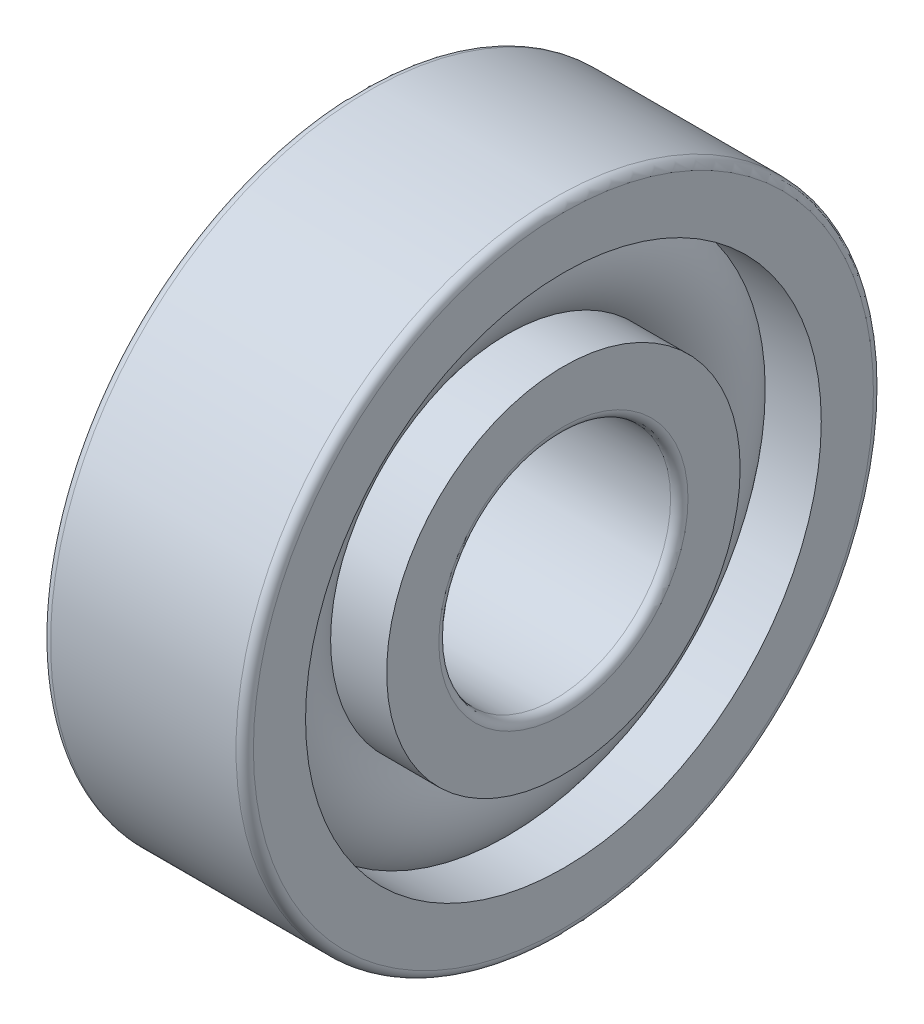
SolidWorks part; units mm, degrees
ref_plane "Plane1" through (0, 0, 0) normal (0, 0, 1) x (1, 0, 0)
ref_plane "Plane2" through (0, 0, 0) normal (0, 1, 0) x (1, 0, 0)
ref_plane "Plane3" through (0, 0, 0) normal (1, 0, 0) x (0, 0, -1)
sketch "Clipboard" plane through (0, 0, 0) normal (0, 0, 1) x (1, 0, 0)
  line L0 (-10, 0) -> (10, 0) construction
  line L1 (0, 0) -> (22.3471, -0.7804)
  line L2 (0, 0) -> (7.4954, 0.2617)
  line L3 (0, 0) -> (22.3471, -0.7804)
  line L4 (0, 0) -> (-22.3573, -0.3902)
sketch "CagSpiSke" plane through (0, 0, 0) normal (0, 0, 1) x (1, 0, 0)
  line L0 (0.21, 7.15) -> (0.21, 7.85)
  line L1 (0.21, 7.85) -> (-0.21, 7.85)
  line L2 (-0.21, 7.85) -> (-0.21, 7.15)
  line L3 (-0.21, 7.15) -> (0.21, 7.15)
  line L4 (-20.6375, 0) -> (20.6375, 0) construction
  line L5 (0, 0) -> (0, 23.7692) construction
revolve "CageSpine" add sketch "CagSpiSke" angle 0.001 about L4 reverse direction yes
ref_axis "Axis1" through (-50, 0, 0) along (1, 0, 0)
sketch "CagBalSke" plane through (0, 0, 0) normal (0, 0, 1) x (1, 0, 0)
  line L0 (-2.31, 7.5) -> (2.31, 7.5)
  line L1 (-1.905, 7.5) -> (1.905, 7.5) construction
  line L2 (-10, 0) -> (10, 0) construction
  line L3 (0, 0) -> (0, 24) construction
  arc A0 (2.31, 7.5) -> (-2.31, 7.5) centre (0, 7.5) cw
revolve "CageBall" [suppressed] add sketch "CagBalSke" angle 360 about L1 reverse direction yes
pattern_circular "CageBalls" [suppressed] count 2 every 180 about axis through (-50, 0, 0) along (1, 0, 0)
sketch "CagTrmODSke" plane through (0, 0, 0) normal (0, 0, 1) x (1, 0, 0)
  line L0 (2.311, 7.85) -> (2.311, 9.811)
  line L1 (2.311, 9.811) -> (-2.311, 9.811)
  line L2 (-2.311, 9.811) -> (-2.311, 7.85)
  line L3 (-2.311, 7.85) -> (2.311, 7.85)
  line L4 (-20.6375, 0) -> (20.6375, 0) construction
  line L5 (0, 0) -> (0, 25) construction
revolve "CageTrimOD" [suppressed] cut sketch "CagTrmODSke" angle 360 about L4 reverse direction yes
sketch "CagTrmIDSke" plane through (0, 0, 0) normal (0, 0, 1) x (1, 0, 0)
  line L0 (2.311, 5.191) -> (2.311, 7.15)
  line L1 (2.311, 7.15) -> (-2.311, 7.15)
  line L2 (-2.311, 7.15) -> (-2.311, 5.191)
  line L3 (-2.311, 5.191) -> (2.311, 5.191)
  line L4 (-20.6375, 0) -> (20.6375, 0) construction
  line L5 (0, 0) -> (0, 25) construction
revolve "CageTrimID" [suppressed] cut sketch "CagTrmIDSke" angle 360 about L4 reverse direction yes
sketch "BalSimSke" plane through (0, 0, 0) normal (0, 0, 1) x (1, 0, 0)
  line L0 (-10, 0) -> (10, 0) construction
  line L1 (-10, 7.5) -> (10, 7.5) construction
  line L2 (0, 0) -> (0, 23) construction
  circle A0 centre (0, 7.5) radius 2.1
revolve "BallsSimplified" add sketch "BalSimSke" angle 360 about L0
sketch "BalDetSke" plane through (0, 0, 0) normal (0, 0, 1) x (1, 0, 0)
  line L0 (-2.1, 7.5) -> (2.1, 7.5)
  line L1 (-1.905, 7.5) -> (1.905, 7.5) construction
  line L2 (0, 0) -> (0, 25) construction
  arc A0 (2.1, 7.5) -> (-2.1, 7.5) centre (0, 7.5) cw
revolve "BallDetailed" [suppressed] add sketch "BalDetSke" angle 360 about L1 reverse direction yes
sketch "InnRacSke" plane through (0, 0, 0) normal (0, 0, 1) x (1, 0, 0)
  line L0 (-1.5315, 6.1) -> (-3.5, 6.1)
  line L1 (-3.5, 6.1) -> (-3.5, 4.3)
  line L2 (-3.2, 4) -> (3.2, 4)
  line L3 (3.5, 4.3) -> (3.5, 6.1)
  line L4 (3.5, 6.1) -> (1.5315, 6.1)
  line L5 (-20.6375, 0) -> (20.6375, 0) construction
  line L6 (0, 0) -> (0, 30) construction
  arc A0 (-3.5, 4.3) -> (-3.2, 4) centre (-3.2, 4.3) ccw
  arc A1 (3.2, 4) -> (3.5, 4.3) centre (3.2, 4.3) ccw
  arc A2 (1.5315, 6.1) -> (-1.5315, 6.1) centre (0, 7.5) cw
revolve "InnerRace" add sketch "InnRacSke" angle 360 about L5 reverse direction yes
sketch "OutRacSke" plane through (0, 0, 0) normal (0, 0, 1) x (1, 0, 0)
  line L0 (-1.5315, 8.9) -> (-3.5, 8.9)
  line L1 (-3.5, 8.9) -> (-3.5, 10.7)
  line L2 (-3.2, 11) -> (3.2, 11)
  line L3 (3.5, 10.7) -> (3.5, 8.9)
  line L4 (3.5, 8.9) -> (1.5315, 8.9)
  line L5 (-20.6375, 0) -> (20.6375, 0) construction
  line L6 (0, 0) -> (0, 30) construction
  arc A0 (-3.5, 10.7) -> (-3.2, 11) centre (-3.2, 10.7) cw
  arc A1 (3.2, 11) -> (3.5, 10.7) centre (3.2, 10.7) cw
  arc A2 (1.5315, 8.9) -> (-1.5315, 8.9) centre (0, 7.5) ccw
revolve "OuterRace" add sketch "OutRacSke" angle 360 about L5 reverse direction yes
pattern_circular "BallsDetailed" [suppressed] count 2 every 180 about axis through (-50, 0, 0) along (1, 0, 0)
equation "\"BallCLRad@Clipboard\" = ( \"OD@OutRacSke\" + \"ID@InnRacSke\" ) / 4"
equation "\"BallCLRad@BalSimSke\" = \"BallCLRad@Clipboard\""
equation "\"BallCLRad@BalDetSke\" = \"BallCLRad@Clipboard\""
equation "\"BallCLRad@InnRacSke\" = \"BallCLRad@Clipboard\""
equation "\"BallCLRad@OutRacSke\" = \"BallCLRad@Clipboard\""
equation "\"Ball_diameter@InnRacSke\" = \"Ball_diameter@BalDetSke\" - 0.05"
equation "\"Ball_diameter@OutRacSke\" = \"Ball_diameter@BalDetSke\" - 0.05"
equation "\"Ball_diameter@BalSimSke\" = \"Ball_diameter@BalDetSke\""
equation "\"Width@OutRacSke\" = \"Width@InnRacSke\""
equation "\"Fillet_radius@OutRacSke\" = \"Fillet_radius@InnRacSke\""
equation "\"Max_count@Clipboard\" = int( 3.14159265 / atn(( \"Ball_diameter@BalDetSke\" / 2) / sqr( \"BallCLRad@Clipboard\"  *  \"BallCLRad@Clipboard\" - ( \"Ball_diameter@BalDetSke\" / 2) *  ( \"Ball_diameter@BalDetSke\" / 2))))"
equation "\"Max_count@Clipboard\" = ((sgn( \"Max_count@Clipboard\" - \"Count@Clipboard\" )-1)*( \"Max_count@Clipboard\" - \"Count@Clipboard\" ))/-2+ \"Count@Clipboard\""
equation "\"Count@BallsDetailed\" = int( \"Show_count@Clipboard\" ) "
equation "\"Count@BallsDetailed\" = ((sgn( \"Count@BallsDetailed\" - \"Max_count@Clipboard\" )-1)*( \"Count@BallsDetailed\" - \"Max_count@Clipboard\" ))/-2+ \"Max_count@Clipboard\""
equation "\"Count@BallsDetailed\" = ((sgn( \"Count@BallsDetailed\" - \"Min_count@Clipboard\" )+1)*( \"Count@BallsDetailed\" - \"Min_count@Clipboard\"))/2 +\"Min_count@Clipboard\""
equation "\"Angle@BallsDetailed\" = 360.0 / \"Max_count@Clipboard\""
equation "\"BallCLRad@CagBalSke\" = \"BallCLRad@Clipboard\""
equation "\"Count@CageBalls\" = \"Count@BallsDetailed\""
equation "\"Angle@CageBalls\" = \"Angle@BallsDetailed\""
equation "\"Angle@CageSpine\" =  \"Angle@CageBalls\" * ( \"Count@CageBalls\" -1 + int( \"Count@CageBalls\" / \"Max_count@Clipboard\" ) )  + 0.001 -  int( \"Count@CageBalls\" / \"Max_count@Clipboard\" ) * 0.001"
equation "\"Angle@CageSpine\" =  \"Angle@CageSpine\" * int( \"Min_count@Clipboard\" / 2) + int(1 / \"Min_count@Clipboard\")  * 0.001"
equation "\"CageWallOD@CagBalSke\" =  \"Ball_diameter@BalDetSke\" * 1.1"
equation "\"Thickness@CagSpiSke\" =  \"Ball_diameter@BalDetSke\" * 0.1"
equation "\"OD@CagTrmODSke\" = \"BallCLRad@Clipboard\" * 2 + \"CageWallOD@CagBalSke\" + 0.002"
equation "\"ID@CagTrmODSke\" = \"BallCLRad@Clipboard\" * 2 + \"Ball_diameter@BalDetSke\" / 6"
equation "\"OD@CagTrmIDSke\" = \"BallCLRad@Clipboard\" * 2 - \"Ball_diameter@BalDetSke\" / 6"
equation "\"ID@CagTrmIDSke\" = \"BallCLRad@Clipboard\" * 2 - \"CageWallOD@CagBalSke\" + 0.002"
equation "\"OD@CagSpiSke\" = \"ID@CagTrmODSke\""
equation "\"ID@CagSpiSke\" = \"OD@CagTrmIDSke\""
equation "\"Width@CagTrmODSke\" = \"CageWallOD@CagBalSke\" + 0.002"
equation "\"Width@CagTrmIDSke\" = \"CageWallOD@CagBalSke\" + 0.002"
